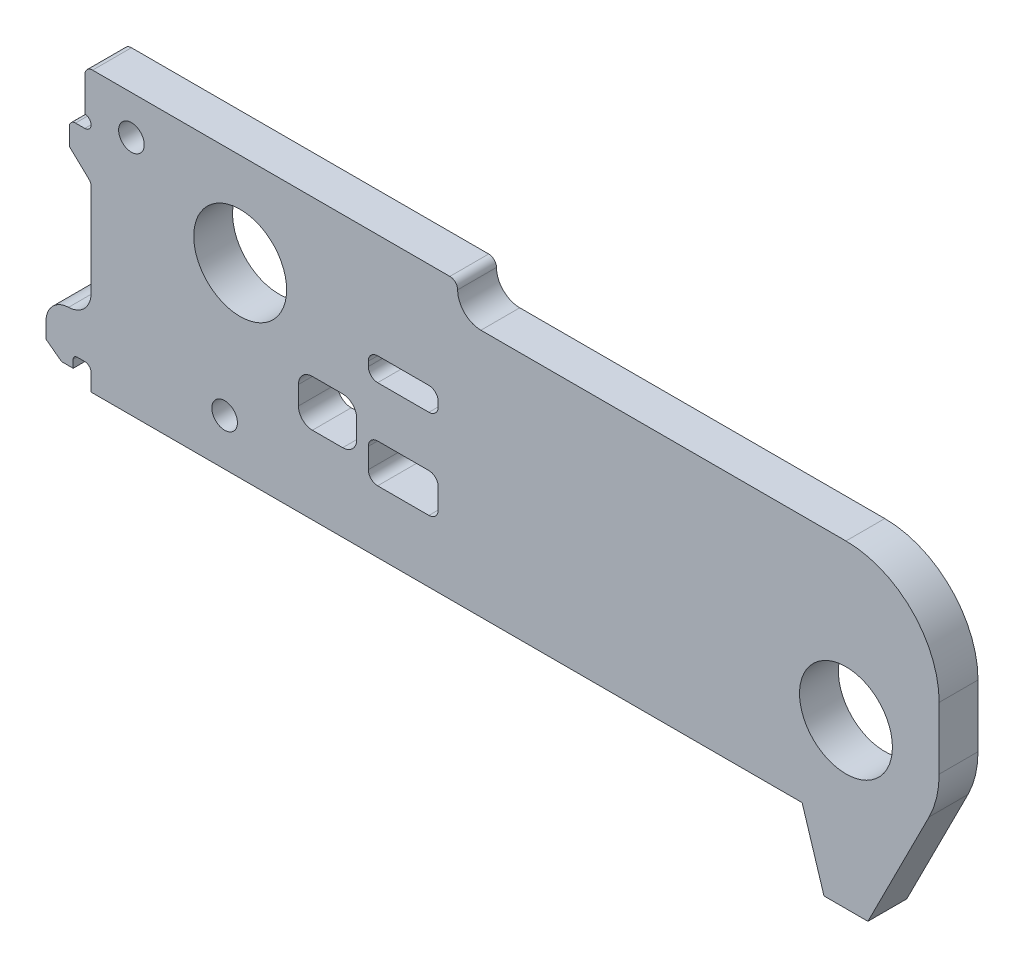
SolidWorks part; units mm, degrees
material "6061-T6 Black anodised"
ref_plane "Front Plane" through (0, 0, 0) normal (0, 0, 1) x (1, 0, 0)
ref_plane "Top Plane" through (0, 0, 0) normal (0, 1, 0) x (1, 0, 0)
ref_plane "Right Plane" through (0, 0, 0) normal (1, 0, 0) x (0, 0, -1)
sketch "Sketch1" plane through (0, 0, 0) normal (0, 0, 1) x (1, 0, 0)
  line L0 (72.3566, -24) -> (75.1721, -33)
  line L1 (-20, 12) -> (28, 12)
  line L2 (-20, 12) -> (-20, 6.6)
  line L3 (-19.2, -24) -> (72.3566, -24)
  line L4 (90, -4) -> (90, -12)
  line L5 (75.1721, -33) -> (80.8279, -33)
  line L6 (88.7087, -17.4151) -> (80.8279, -33)
  line L7 (25.5, -4.5) -> (25.5, -11) construction
  line L8 (16.5, -11) -> (25.5, -11)
  line L9 (16.5, -11) -> (16.5, -16)
  line L10 (16.5, -16) -> (25.5, -16)
  line L11 (25.5, -11) -> (25.5, -16)
  line L12 (16.5, -1.5) -> (25.5, -1.5)
  line L13 (16.5, -1.5) -> (16.5, -4.5)
  line L14 (16.5, -4.5) -> (25.5, -4.5)
  line L15 (25.5, -1.5) -> (25.5, -4.5)
  line L16 (28, 12) -> (28, 8)
  line L17 (7.5, -8) -> (15, -8)
  line L18 (7.5, -8) -> (7.5, -14)
  line L19 (7.5, -14) -> (15, -14)
  line L20 (15, -8) -> (15, -14)
  line L21 (28, 8) -> (78, 8)
  line L22 (-20, 5) -> (-22, 5)
  line L23 (-22, 5) -> (-22, 2)
  line L24 (-22, 2) -> (-19.4494, -0.4196)
  line L25 (-19.2, -1) -> (-19.2, -13)
  line L26 (-25, -21) -> (-25, -16)
  line L27 (-25, -21) -> (-23, -22.5)
  line L28 (-23, -22.5) -> (-21.5, -22.5)
  line L29 (-21.5, -22.5) -> (-21.5, -21.5)
  line L30 (-21, -21) -> (-20, -21)
  line L31 (-19.2, -21.8) -> (-19.2, -24)
  line L32 (-25, -16) -> (-22.2, -16)
  circle A0 centre (0, 0) radius 5.98
  circle A1 centre (78, -12) radius 5.98
  arc A2 (-20, 5) -> (-20, 6.6) centre (-20, 5.8) ccw
  arc A3 (88.7087, -17.4151) -> (90, -12) centre (78, -12) ccw
  circle A4 centre (-14, 7) radius 1.65
  circle A5 centre (-2, -18) radius 1.65
  arc A6 (90, -4) -> (78, 8) centre (78, -4) ccw
  arc A7 (-22.2, -16) -> (-19.2, -13) centre (-22.2, -13) ccw
  arc A8 (-19.2, -1) -> (-19.4494, -0.4196) centre (-20, -1) ccw
  arc A9 (-19.2, -21.8) -> (-20, -21) centre (-20, -21.8) ccw
  arc A10 (-21.5, -21.5) -> (-21, -21) centre (-21, -21.5) cw
  point P4 (-20, -6)
  point P13 (78, -33)
  point P29 (25.5, -10)
  dimension "D3" = 11.96
  dimension "D4" = 98
  dimension "D8" = 3.3
  dimension "D10" = 13
  dimension "D11" = 10
  dimension "D12" = 12
  dimension "D23" = 12
  dimension "D33" = 0.8
  dimension "D34" = 0.5
  dimension "D39" = 3
  dimension "D1" = 9
  dimension "D5" = 20
  dimension "D6" = 36
  dimension "D7" = 4
  dimension "D9" = 14
  dimension "D13" = 5.5
  dimension "D14" = 5
  dimension "D15" = 3
  dimension "D16" = 9
  dimension "D17" = 16.5
  dimension "D18" = 11
  dimension "D19" = 9
  dimension "D20" = 7.5
  dimension "D21" = 8
  dimension "D22" = 6
  dimension "D24" = 48
  dimension "D25" = 12
  dimension "D26" = 24
  dimension "D27" = 2
  dimension "D28" = 1.5
  dimension "D29" = 1.5
  dimension "D30" = 33
  dimension "D31" = 5
  dimension "D32" = 5
  dimension "D35" = 7
  dimension "D36" = 6
  dimension "D37" = 3
  dimension "D38" = 2
  dimension "D40" = 1.5
extrude "Boss-Extrude1" add sketch "Sketch1" along normal blind 5
fillet "Fillet1" radius 1.2 8 edges at (16.5, -4.5, 2.5) (16.5, -1.5, 2.5) (25.5, -1.5, 2.5) (25.5, -4.5, 2.5) (25.5, -16, 2.5) (25.5, -11, 2.5) (16.5, -11, 2.5) (16.5, -16, 2.5)
fillet "Fillet2" radius 3 1 edges at (28, 8, 2.5)
fillet "Fillet3" radius 1 2 edges at (28, 12, 2.5) (-20, 12, 2.5)
sketch "Sketch2" plane through (0, 0, 5) normal (0, 0, 1) x (1, 0, 0)
  line L0 (35, -13) -> (68, -19) construction
  line L1 (35, -13) -> (68, -13)
  line L2 (35, -13) -> (35, -15.25)
  line L3 (35, -19) -> (68, -19)
  line L4 (68, -13) -> (68, -15.25)
  line L5 (36.5, -15.25) -> (35, -15.25)
  line L6 (36.5, -15.25) -> (36.5, -16.75)
  line L7 (36.5, -16.75) -> (35, -16.75)
  line L8 (68, -16.75) -> (68, -19)
  line L9 (36.5, -15.25) -> (35, -16.75) construction
  line L10 (36.5, -16.75) -> (35, -15.25) construction
  line L11 (66.5, -15.25) -> (68, -15.25)
  line L12 (66.5, -15.25) -> (66.5, -16.75)
  line L13 (66.5, -16.75) -> (68, -16.75)
  line L14 (-19.2, -24) -> (72.3566, -24) construction
  line L15 (66.5, -15.25) -> (68, -16.75) construction
  line L16 (66.5, -16.75) -> (68, -15.25) construction
  line L17 (68, -13) -> (35, -19) construction
  line L18 (35, -16.75) -> (35, -19)
  point P4 (35.75, -16)
  point P9 (67.25, -16)
  point P14 (51.5, -16)
  dimension "D1" = 1.5
  dimension "D2" = 33
  dimension "D3" = 6
  dimension "D4" = 1.5
  dimension "D5" = 68
  dimension "D6" = 5
extrude "Cut-Extrude1" [suppressed] cut sketch "Sketch2" against normal through all
fillet "Fillet4" [suppressed] radius 0.5
fillet "Fillet5" radius 1.8 4 edges at (15, -14, 2.5) (15, -8, 2.5) (7.5, -8, 2.5) (7.5, -14, 2.5)
sketch "Sketch3" plane through (0, 0, 5) normal (0, 0, 1) x (1, 0, 0)
  line L0 (78, -6.02) -> (66.5, -6.02)
  line L1 (66, -6.02) -> (66, -6.52) construction
  line L2 (66, -6.52) -> (75.6063, -6.52)
  line L3 (78, -12) -> (66, -12)
  line L4 (66, -12) -> (66, -11.5) construction
  line L5 (66.5, -11.5) -> (72.0409, -11.5)
  line L6 (78, -6.02) -> (78, -12)
  line L7 (0, 0) -> (12, 0)
  line L8 (12, 0) -> (12, 0.5) construction
  line L9 (11.5, 0.5) -> (5.9591, 0.5)
  line L10 (0, 0) -> (0, 5.98)
  line L11 (0, 5.98) -> (11.5, 5.98)
  line L12 (12, 5.98) -> (12, 5.48) construction
  line L13 (12, 5.48) -> (2.3937, 5.48)
  circle A0 centre (78, -12) radius 5.98 construction
  arc A1 (75.6063, -6.52) -> (72.0409, -11.5) centre (78, -12) ccw
  arc A2 (66.5, -6.02) -> (66, -6.52) centre (66, -6.02) ccw
  arc A3 (66.5, -11.5) -> (66, -12) centre (66, -11.5) ccw
  circle A4 centre (0, 0) radius 5.98 construction
  arc A5 (5.9591, 0.5) -> (2.3937, 5.48) centre (0, 0) ccw
  arc A6 (12, 5.48) -> (11.5, 5.98) centre (12, 5.98) ccw
  arc A7 (12, 0) -> (11.5, 0.5) centre (12, 0.5) ccw
  dimension "D3" = 0.5
  dimension "D1" = 0.5
  dimension "D2" = 12
extrude "Cut-Extrude2" [suppressed] cut sketch "Sketch3" against normal through all
fillet "Fillet6" radius 0.8 1 edges at (-22, 5, 2.5)
fillet "Fillet7" radius 3 1 edges at (-25, -16, 2.5)
equation "\"y-cross-rib-thickness\"=6"
equation "\"y-rib-thickness\"=6"
equation "\"bed-plate-thickness\"=6"
equation "\"x-plate-thickness\"=5"
equation "\"rod-diameter\"=12"
equation "\"t-nut-hole-diameter\"=3"
equation "\"y-plate-thickness\"=5"
equation "\"D1@Boss-Extrude1\"=\"y-plate-thickness\""
